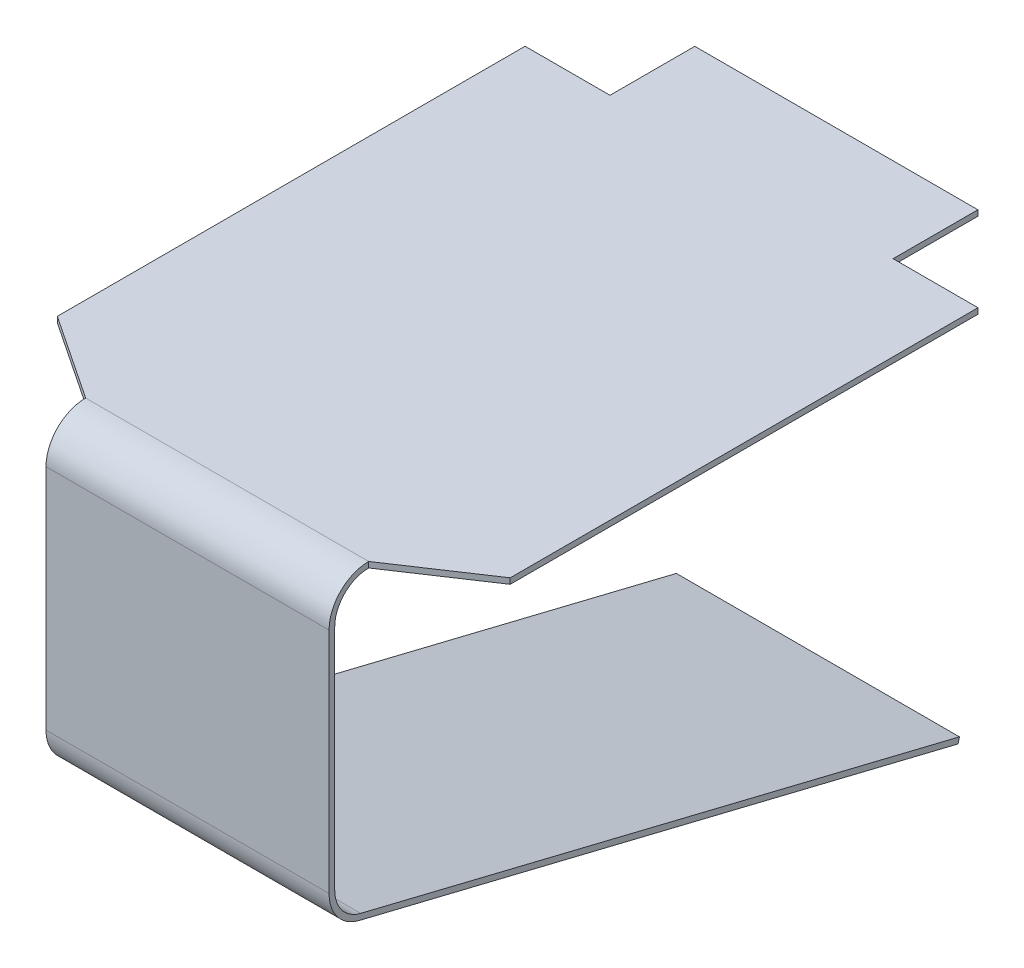
SolidWorks part; units mm, degrees
ref_plane "Спереди" through (0, 0, 0) normal (0, 0, 1) x (1, 0, 0)
ref_plane "Сверху" through (0, 0, 0) normal (0, 1, 0) x (1, 0, 0)
ref_plane "Справа" through (0, 0, 0) normal (1, 0, 0) x (0, 0, -1)
sketch "Эскиз1" plane through (0, 0, 0) normal (1, 0, 0) x (0, 0, -1)
  line L0 (0, 0) -> (-5.38, 0)
  line L1 (-5.68, -0.3) -> (-5.68, -2.3146)
  line L2 (-5.4513, -2.606) -> (-0.1628, -3.9)
  arc A0 (-5.68, -2.3146) -> (-5.4513, -2.606) centre (-5.38, -2.3146) ccw
  arc A1 (-5.68, -0.3) -> (-5.38, 0) centre (-5.38, -0.3) cw
  point P7 (-5.68, -2.55)
  point P10 (-5.68, 0)
  dimension "D5" = 0.3
  dimension "D1" = 5.68
  dimension "D2" = 2.55
  dimension "D3" = 5.68
  dimension "D4" = 3.9
extrude "Вытянуть-Тонкостенный1" add sketch "Эскиз1" along normal blind 1.25 and the other way blind 1.25 thin thin type one direction wall 0.05
sketch "Эскиз2" plane through (1.25, 0, 0) normal (1, 0, 0) x (0, 0, -1)
  line L0 (0, 0) -> (-5.38, 0) construction
  line L1 (-5.38, 0.05) -> (-0.7488, 0.05)
  line L2 (-5.38, 0.05) -> (-5.38, 0)
  line L3 (-5.38, 0) -> (-0.7488, 0)
  line L4 (-0.7488, 0.05) -> (-0.7488, 0)
extrude "Бобышка-Вытянуть1" add sketch "Эскиз2" along normal blind 0.75
chamfer "Фаска1" distance 0.75 distance2 0.5 1 edges at (2, 0.025, 5.38) first distance on face at (1.625, 0.025, 5.38)
ref_plane "Плоскость1" through (0, 0, 0) normal (1, 0, 0) x (0, 0, -1)
mirror "Зеркальное отражение1" about plane through (0, 0, 0) normal (1, 0, 0) of "Бобышка-Вытянуть1"
chamfer "Фаска2" distance 0.5 distance2 0.75 1 edges at (-2, 0.025, 5.38) first distance on face at (-2, 0.025, 3.0644)
